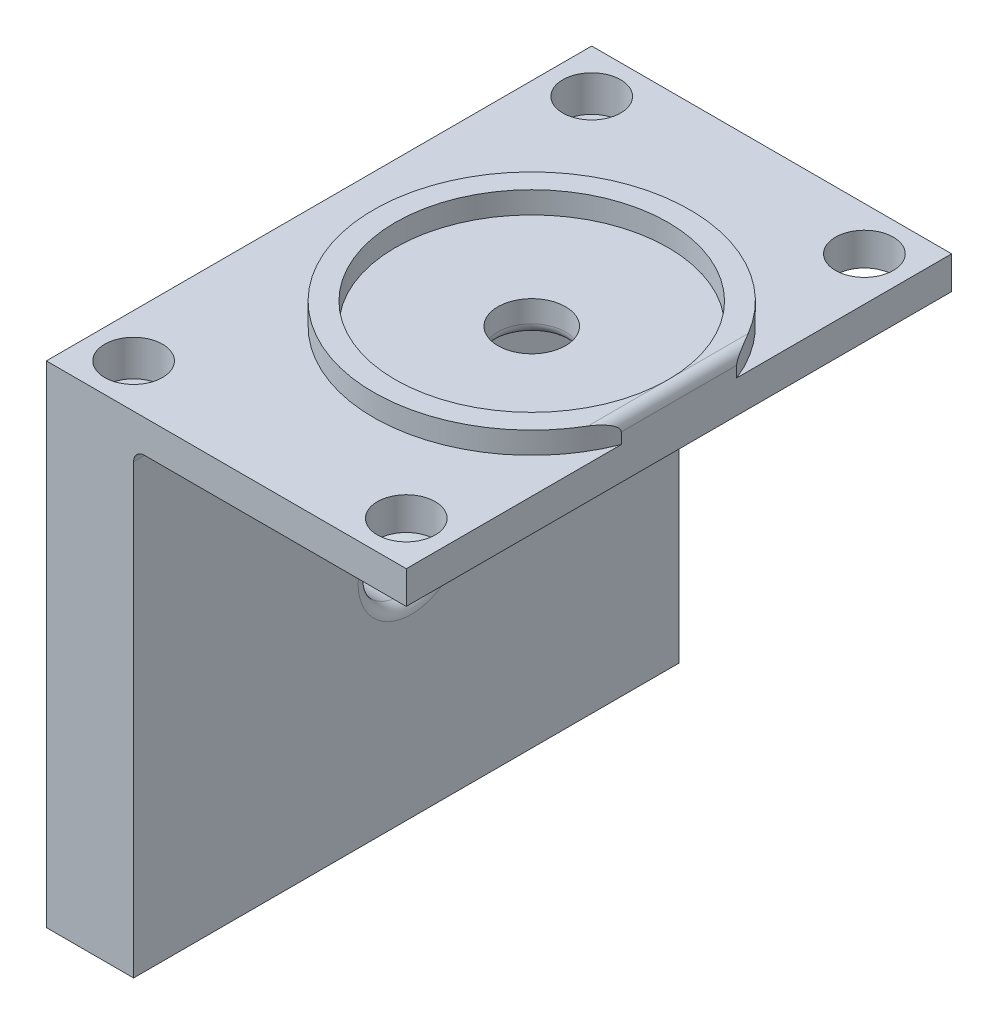
SolidWorks part; units mm, degrees
ref_plane "Front Plane" through (0, 0, 0) normal (0, 0, 1) x (1, 0, 0)
ref_plane "Top Plane" through (0, 0, 0) normal (0, 1, 0) x (1, 0, 0)
ref_plane "Right Plane" through (0, 0, 0) normal (1, 0, 0) x (0, 0, -1)
sketch "Sketch1" plane through (0, 0, 0) normal (0, 1, 0) x (1, 0, 0)
  line L1 (-10.223, 36.3848) -> (14.777, 36.3848)
  line L2 (-10.223, 36.3848) -> (-10.223, -13.6152)
  line L3 (-10.223, -13.6152) -> (14.777, -13.6152)
  line L4 (14.777, 36.3848) -> (14.777, -13.6152)
  circle A0 centre (1.277, 11.3848) radius 3.1
  dimension "D3" = 6.2
  dimension "D1" = 50
  dimension "D2" = 25
  dimension "D4" = 13.5
  dimension "D5" = 25
extrude "Boss-Extrude1" add sketch "Sketch1" along normal blind 3
sketch "Sketch2" plane through (-10.223, 0, 0) normal (-1, 0, 0) x (0, 0, 1)
  line L0 (55, 0) -> (-55, 0) construction
  line L1 (-36.3848, 3) -> (13.6152, 3)
  line L2 (-36.3848, 3) -> (-36.3848, 0)
  line L3 (-36.3848, 0) -> (13.6152, 0)
  line L4 (13.6152, 3) -> (13.6152, 0)
  line L5 (13.6152, 3) -> (13.6152, 0) construction
extrude "Boss-Extrude2" add sketch "Sketch2" along normal blind 8
sketch "Sketch3" plane through (0, 0, 0) normal (0, -1, 0) x (1, 0, 0)
  line L0 (-18.223, 13.6152) -> (14.777, 13.6152) construction
  line L1 (-18.223, -36.3848) -> (-10.223, -36.3848)
  line L2 (-18.223, -36.3848) -> (-18.223, 13.6152)
  line L3 (-18.223, 13.6152) -> (-10.223, 13.6152)
  line L4 (-10.223, -36.3848) -> (-10.223, 13.6152)
  dimension "D1" = 8
extrude "Boss-Extrude3" add sketch "Sketch3" along normal blind 42
sketch "Sketch4" plane through (0, 3, 0) normal (0, 1, 0) x (1, 0, 0)
  line L0 (-18.223, -13.6152) -> (-18.223, 36.3848) construction
  line L1 (14.777, 36.3848) -> (-18.223, 36.3848) construction
  line L2 (-18.223, -13.6152) -> (14.777, -13.6152) construction
  circle A0 centre (-14.223, 32.3848) radius 2.65
  circle A1 centre (-14.223, -9.6152) radius 2.65
  dimension "D2" = 5.3
  dimension "D4" = 5.3
  dimension "D5" = 4
  dimension "D6" = 4
  dimension "D1" = 4
  dimension "D3" = 4
extrude "Cut-Extrude1" cut sketch "Sketch4" against normal blind 3.3
ref_plane "Plane1" through (0, -19.5, 0) normal (0, 1, 0) x (1, 0, 0)
mirror "Mirror1" about plane through (0, -19.5, 0) normal (0, 1, 0) of "Cut-Extrude1"
fillet "Fillet1" radius 1 1 edges at (1.277, 0, -8.2848)
sketch "Sketch5" plane through (-18.223, 0, 0) normal (-1, 0, 0) x (0, 0, 1)
  line L0 (55, 0) -> (-55, 0) construction
  line L1 (-8.6015, -23.1212) -> (-8.3819, -19.2592) construction
  line L2 (-8.3819, -19.2592) -> (-11.6167, -17.138) construction
  line L3 (-11.6167, -17.138) -> (-15.0711, -18.8788) construction
  line L4 (-15.0711, -18.8788) -> (-15.2907, -22.7408) construction
  line L5 (-15.2907, -22.7408) -> (-12.0559, -24.862) construction
  line L6 (-12.0559, -24.862) -> (-8.6015, -23.1212) construction
  circle A0 centre (-11.8363, -21) radius 3.35 construction
  circle A1 centre (-11.8363, -21) radius 3.8682
  dimension "D1" = 21
  dimension "D2" = 6.7
extrude "Cut-Extrude2" cut sketch "Sketch5" against normal blind 9
fillet "Fillet2" radius 1 1 edges at (-10.223, -21, -7.968)
ref_plane "Plane2" through (-1.723, 0, 0) normal (-1, 0, 0) x (0, 0, 1)
mirror "Mirror2" about plane through (-1.723, 0, 0) normal (-1, 0, 0) of "Cut-Extrude1"
sketch "Sketch6" plane through (0, 3, 0) normal (0, 1, 0) x (1, 0, 0)
  line L0 (1.277, 14.4848) -> (1.277, 8.2848) construction
  line L1 (14.777, -13.6152) -> (14.777, 36.3848) construction
  line L2 (14.777, 16.6763) -> (14.777, 6.0933)
  circle A0 centre (1.277, 11.3848) radius 3.1 construction
  circle A1 centre (1.277, 11.3848) radius 3.1
  circle A2 centre (1.277, 11.3848) radius 12.5
  arc A3 (14.777, 16.6763) -> (14.777, 6.0933) centre (1.277, 11.3848) ccw
  line M9 (14.777, -13.6152) -> (14.777, 36.3848)
  dimension "D1" = 25
  dimension "D2" = 2
extrude "Boss-Extrude4" add sketch "Sketch6" along normal blind 2 contours A3 A2 M9
fillet "Fillet3" radius 1 1 edges at (-10.223, 0, -11.3848)
fillet "Fillet4" radius 1 1 edges at (14.777, 5, -11.3848)
